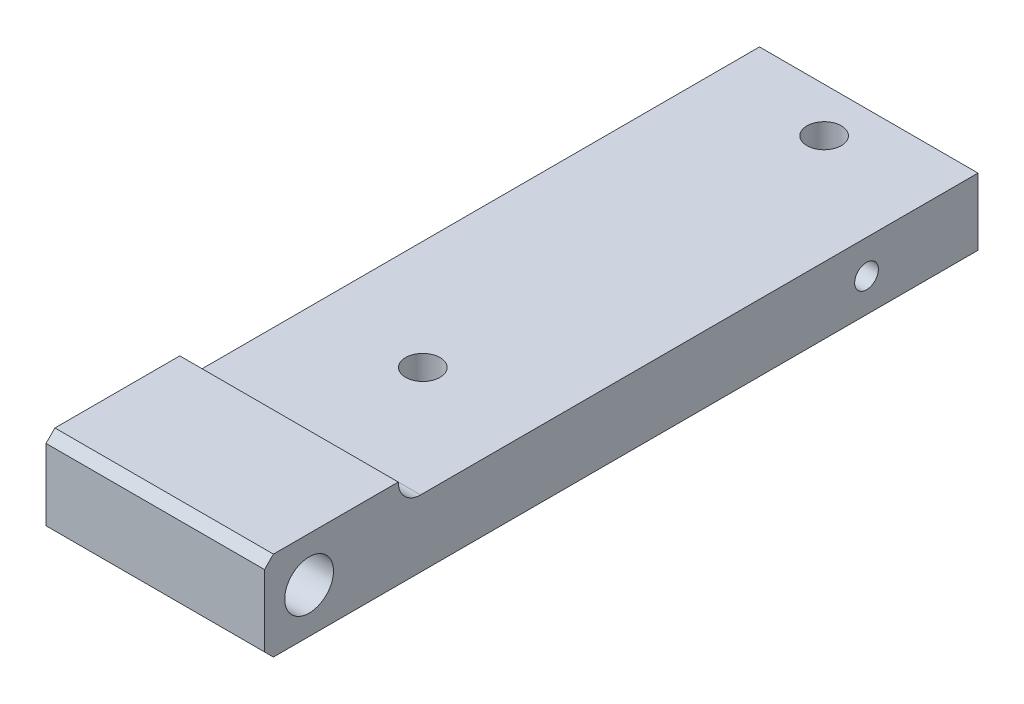
SolidWorks part; units mm, degrees
material "6061-T6 (SS)"
ref_plane "Front" through (0, 0, 0) normal (0, 0, 1) x (1, 0, 0)
ref_plane "Top" through (0, 0, 0) normal (0, 1, 0) x (1, 0, 0)
ref_plane "Right" through (0, 0, 0) normal (1, 0, 0) x (0, 0, -1)
sketch "Sketch1" plane through (0, 0, 0) normal (0, 0, 1) x (1, 0, 0)
  line L1 (-31.115, -12.7) -> (31.115, -12.7)
  line L2 (-31.115, -12.7) -> (-31.115, 12.7)
  line L3 (-31.115, 12.7) -> (31.115, 12.7)
  line L4 (31.115, -12.7) -> (31.115, 12.7)
  line L5 (-31.115, -12.7) -> (31.115, 12.7) construction
  line L6 (-31.115, 12.7) -> (31.115, -12.7) construction
  point P0 (0, 0)
  dimension "D1" = 62.23
  dimension "D2" = 25.4
extrude "Boss-Extrude1" add sketch "Sketch1" along normal blind 203.2
sketch "Sketch2" plane through (31.115, 0, 0) normal (1, 0, 0) x (0, 0, -1)
  line L0 (-203.2, 0) -> (-190.5, 0) construction
  line L1 (-203.2, -12.7) -> (-203.2, 12.7) construction
  dimension "D1" = 12.7
sketch "Sketch5" plane through (0, 12.7, 0) normal (0, 1, 0) x (1, 0, 0)
  line L0 (0, 0) -> (0, -12.7) construction
  line L1 (0, -12.7) -> (0, -127) construction
  line L2 (31.115, -203.2) -> (-31.115, -203.2) construction
  point P3 (0, -203.2)
  dimension "D1" = 12.7
  dimension "D2" = 76.2
  dimension "D3" = 114.3
hole_wizard "3/8 Clearance Hole1" positions "Sketch7" profile "Sketch6" hole size "3/8" standard "ANSI Inch" end condition through all
sketch "Sketch7" plane through (0, 12.7, 0) normal (0, 1, 0) x (1, 0, 0)
  point P0 (0, -12.7)
  point P3 (0, -127)
sketch "Sketch6" plane through (0, 12.7, 12.7) normal (1, 0, 0) x (0, 0, 1)
  line L0 (0, 0) -> (0, 25.4)
  line L1 (0, 25.4) -> (4.9022, 25.4)
  line L2 (4.9022, 25.4) -> (4.9022, 0)
  line L5 (4.9022, 0) -> (0, 0)
  line L11 (0, -6.35) -> (0, 107.95) construction
  dimension "Thru Hole Dia." = 9.8044
  dimension "Thru Hole Depth" = 25.4
sketch "Sketch8" plane through (0, 0, 203.2) normal (0, 0, 1) x (1, 0, 0)
  line L0 (0, 12.7) -> (0, 0) construction
  line L1 (31.115, 12.7) -> (-31.115, 12.7) construction
  line L2 (0, 0) -> (0, -12.7) construction
  line L3 (-31.115, -12.7) -> (31.115, -12.7) construction
hole_wizard "1/2-20 Tapped Hole1" [suppressed] positions "Sketch10" profile "Sketch11" tap size "1/2-20" standard "ANSI Inch"
sketch "Sketch10" plane through (0, 0, 203.2) normal (0, 0, 1) x (1, 0, 0)
  point P0 (0, 0)
sketch "Sketch11" plane through (0, 0, 203.2) normal (1, 0, 0) x (0, -1, 0)
  line L0 (0, 0) -> (0, 35.2076)
  line L1 (0, 35.2076) -> (5.7544, 31.75)
  line L2 (5.7544, 31.75) -> (5.7544, 0)
  line L5 (5.7544, 0) -> (0, 0)
  line L10 (0, 35.2076) -> (-5.7544, 31.75) construction
  line L11 (0, -6.35) -> (0, 107.95) construction
  dimension "Tap Drill Dia." = 11.5087
  dimension "Tap Drill Depth" = 31.75
  dimension "Drill Angle" = 118
cosmetic thread "Hole Thread1" [suppressed] parameters "D1"=25.4, "D2"=12.7
hole_wizard "1/2 Clearance Hole1" positions "Sketch13" profile "Sketch12" hole size "1/2" standard "ANSI Inch" end condition through all
sketch "Sketch13" plane through (31.115, 0, 0) normal (1, 0, 0) x (0, 0, -1)
  point P0 (-190.5, 0)
sketch "Sketch12" plane through (31.115, 0, 190.5) normal (0, 1, 0) x (0, 0, -1)
  line L0 (0, 0) -> (0, 62.23)
  line L1 (0, 62.23) -> (6.9456, 62.23)
  line L2 (6.9456, 62.23) -> (6.9456, 0)
  line L5 (6.9456, 0) -> (0, 0)
  line L11 (0, -6.35) -> (0, 107.95) construction
  dimension "Thru Hole Dia." = 13.8913
  dimension "Thru Hole Depth" = 62.23
sketch "Sketch16" plane through (0, 12.7, 0) normal (0, -1, 0) x (1, 0, 0)
  line L0 (31.115, 0) -> (-31.115, 0) construction
  line L1 (31.115, 165.1) -> (-31.115, 165.1)
  line L2 (31.115, 165.1) -> (31.115, 0)
  line L3 (31.115, 0) -> (-31.115, 0)
  line L4 (-31.115, 165.1) -> (-31.115, 0)
  line L5 (-31.115, 203.2) -> (-31.115, 0) construction
  dimension "D1" = 165.1
extrude "Cut-Extrude2" cut sketch "Sketch16" along normal offset from surface (6.35 mm away) 19.05 up to face at (0, -12.7, 17.6022)
fillet "Fillet1" radius 6.35 1 edges at (0, 6.35, 165.1)
chamfer "Chamfer1" distance 2.54 angle 45 2 edges at (0, -12.7, 203.2) (0, 12.7, 203.2)
sketch "Sketch17" plane through (31.115, 0, 0) normal (1, 0, 0) x (0, 0, -1)
  line L0 (0, -3.175) -> (-31.75, -3.175) construction
  line L1 (0, -12.7) -> (0, 6.35) construction
  dimension "D1" = 31.75
hole_wizard "1/4 Clearance Hole1" positions "Sketch19" profile "Sketch18" hole size "1/4" standard "ANSI Inch" end condition through all
sketch "Sketch19" plane through (31.115, 0, 0) normal (1, 0, 0) x (0, 0, -1)
  point P0 (-31.75, -3.175)
sketch "Sketch18" plane through (31.115, -3.175, 31.75) normal (0, 1, 0) x (0, 0, -1)
  line L0 (0, 0) -> (0, 62.23)
  line L1 (0, 62.23) -> (3.3782, 62.23)
  line L2 (3.3782, 62.23) -> (3.3782, 0)
  line L5 (3.3782, 0) -> (0, 0)
  line L11 (0, -6.35) -> (0, 107.95) construction
  dimension "Thru Hole Dia." = 6.7564
  dimension "Thru Hole Depth" = 62.23
